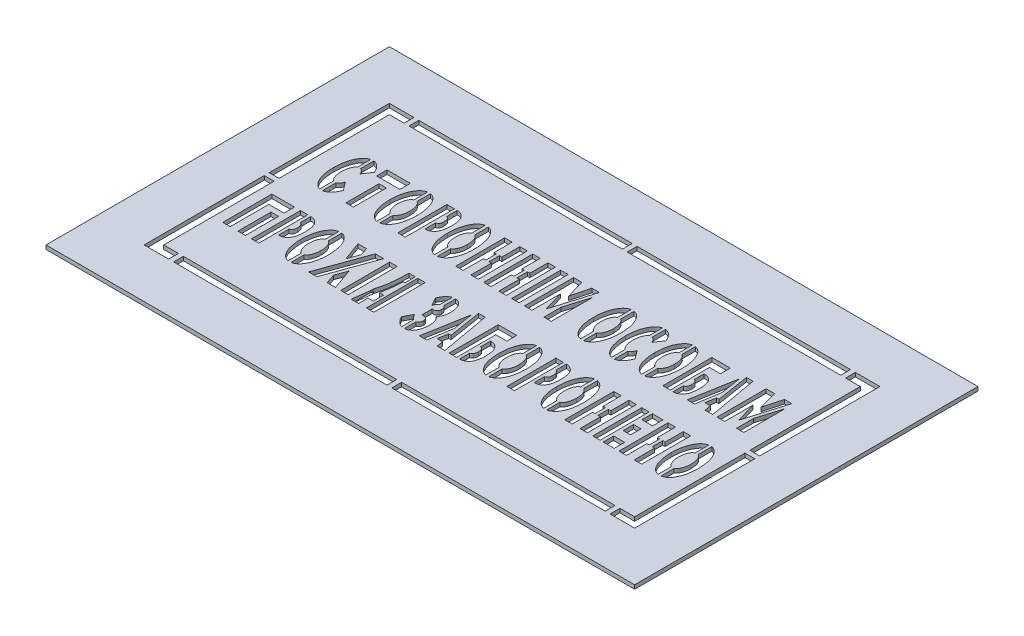
SolidWorks part; units mm, degrees
ref_plane "Спереди" through (0, 0, 0) normal (0, 0, 1) x (1, 0, 0)
ref_plane "Сверху" through (0, 0, 0) normal (0, 1, 0) x (1, 0, 0)
ref_plane "Справа" through (0, 0, 0) normal (1, 0, 0) x (0, 0, -1)
sketch "Эскиз1" plane through (0, 0, 0) normal (0, 1, 0) x (1, 0, 0)
  line L0 (25, 250) -> (25, 240)
  line L1 (0, 250) -> (500, 250)
  line L2 (0, 250) -> (0, 0)
  line L3 (0, 0) -> (500, 0)
  line L4 (500, 250) -> (500, 0)
  line L5 (30, 250) -> (30, 240)
  line L6 (0, 125) -> (-49.6951, 125) construction
  line L7 (10, 240) -> (490, 240)
  line L8 (10, 240) -> (10, 10)
  line L9 (10, 10) -> (490, 10)
  line L10 (490, 240) -> (490, 10)
  line L11 (250, 250) -> (250, 284.0129) construction
  line L12 (470, 250) -> (470, 240)
  line L13 (475, 250) -> (475, 240)
  line L14 (247.5, 250) -> (247.5, 240)
  line L15 (252.5, 250) -> (252.5, 240)
  line L16 (475, 0) -> (475, 10)
  line L17 (470, 0) -> (470, 10)
  line L18 (30, 0) -> (30, 10)
  line L19 (25, 0) -> (25, 10)
  line L20 (252.5, 0) -> (252.5, 10)
  line L21 (247.5, 0) -> (247.5, 10)
  line L22 (0, 127.5) -> (10, 127.5)
  line L23 (0, 122.5) -> (10, 122.5)
  line L24 (500, 122.5) -> (490, 122.5)
  line L25 (500, 127.5) -> (490, 127.5)
  line L27 (-50, -50) -> (550, -50)
  line L28 (-50, -50) -> (-50, 300)
  line L29 (-50, 300) -> (550, 300)
  line L30 (550, -50) -> (550, 300)
  point P0 (0, 0)
  point P6 (0, 0)
  dimension "D1" = 500
  dimension "D2" = 250
  dimension "D3" = 10
  dimension "D4" = 10
  dimension "D5" = 10
  dimension "D6" = 10
  dimension "D7" = 5
  dimension "D8" = 15
  dimension "D9" = 5
  dimension "D10" = 5
  dimension "D11" = 600
  dimension "D12" = 350
  dimension "D13" = 50
  dimension "D14" = 50
extrude "Бобышка-Вытянуть1" add sketch "Эскиз1" along normal blind 4 contours L10 L7 L8 L9 | L19 L3 L18 L9 | L21 L3 L20 L9 | L17 L3 L16 L9 | L4 L25 L10 L24 | L13 L1 L12 L7 | L15 L1 L14 L7 | L0 L7 L5 L1 | L2 L23 L8 L22 | L27 L30 L29 L28 L1 L4 L3 L2 region at (27.5, 0, -245) region at (250, 0, -125) region at (5, 0, -125) region at (250, 0, -245) region at (472.5, 0, -245) region at (27.5, 0, -5) region at (250, 0, -5) region at (495, 0, -125) region at (472.5, 0, -5) region at (-43.0538, 0, -125)
sketch "Эскиз2" plane through (0, 4, 0) normal (0, 1, 0) x (1, 0, 0)
  line L0 (14.7357, 140) -> (485.2643, 140) construction
  line L2 (250, 140) -> (250, 300) construction
  line L3 (-50, 300) -> (550, 300) construction
  line L4 (14.7357, 60) -> (485.2643, 60) construction
  line L5 (485.2643, 60) -> (485.2643, 140) construction
  line L6 (14.7357, 140) -> (14.7357, 60) construction
  line L7 (-50, 125) -> (-122.4254, 125) construction
  line L8 (-50, -50) -> (-50, 300) construction
  line L12 (0, 0) -> (25, 0) construction
  text T0 "СТОРОННІМ ОСОБАМ" font "Sargento Gorila" height 50
  text T1 "ПРОХІД ЗАБОРОНЕНО" font "Sargento Gorila" height 50
  dimension "D1" = 15
  dimension "D2" = 65
  dimension "D3" = 60
extrude "Вырез-Вытянуть1" cut sketch "Эскиз2" against normal blind 4
